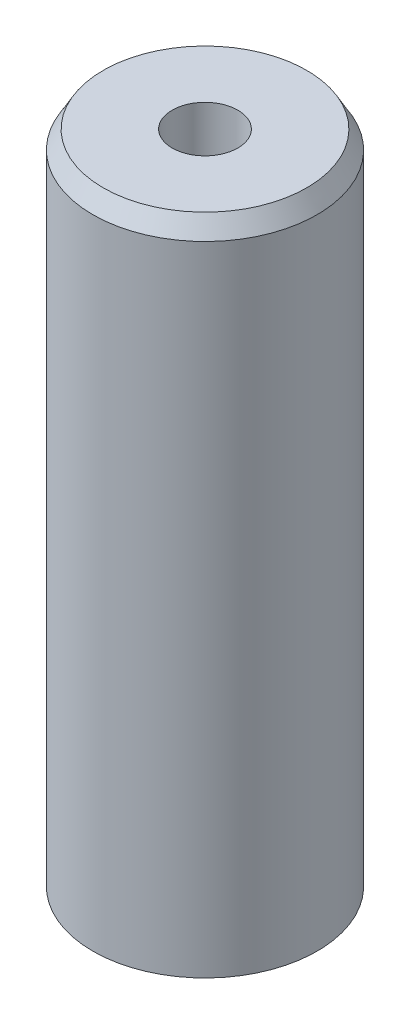
SolidWorks part; units mm, degrees
ref_plane "Front Plane" through (0, 0, 0) normal (0, 0, 1) x (1, 0, 0)
ref_plane "Top Plane" through (0, 0, 0) normal (0, 1, 0) x (1, 0, 0)
ref_plane "Right Plane" through (0, 0, 0) normal (1, 0, 0) x (0, 0, -1)
sketch "Sketch1" plane through (0, 0, 0) normal (0, 1, 0) x (1, 0, 0)
  circle A0 centre (0, 0) radius 32.5
  dimension "SHAFT_OD" = 65
extrude "Boss-Extrude1" add sketch "Sketch1" along normal blind 193.0435
sketch "Sketch2" plane through (0, 0, 0) normal (0, 1, 0) x (1, 0, 0)
  circle A0 centre (0, 0) radius 9.513
  dimension "BORE_D" = 19.026
extrude "Cut-Extrude1" cut sketch "Sketch2" along normal through all
chamfer "Chamfer1" distance 5.2307 angle 29.948 2 edges at (0, 193.0435, 32.5) (0, 0, 32.5) first distance on face at (0, 193.0435, 32.5) first distance on face at (0, 0, 9.513)
